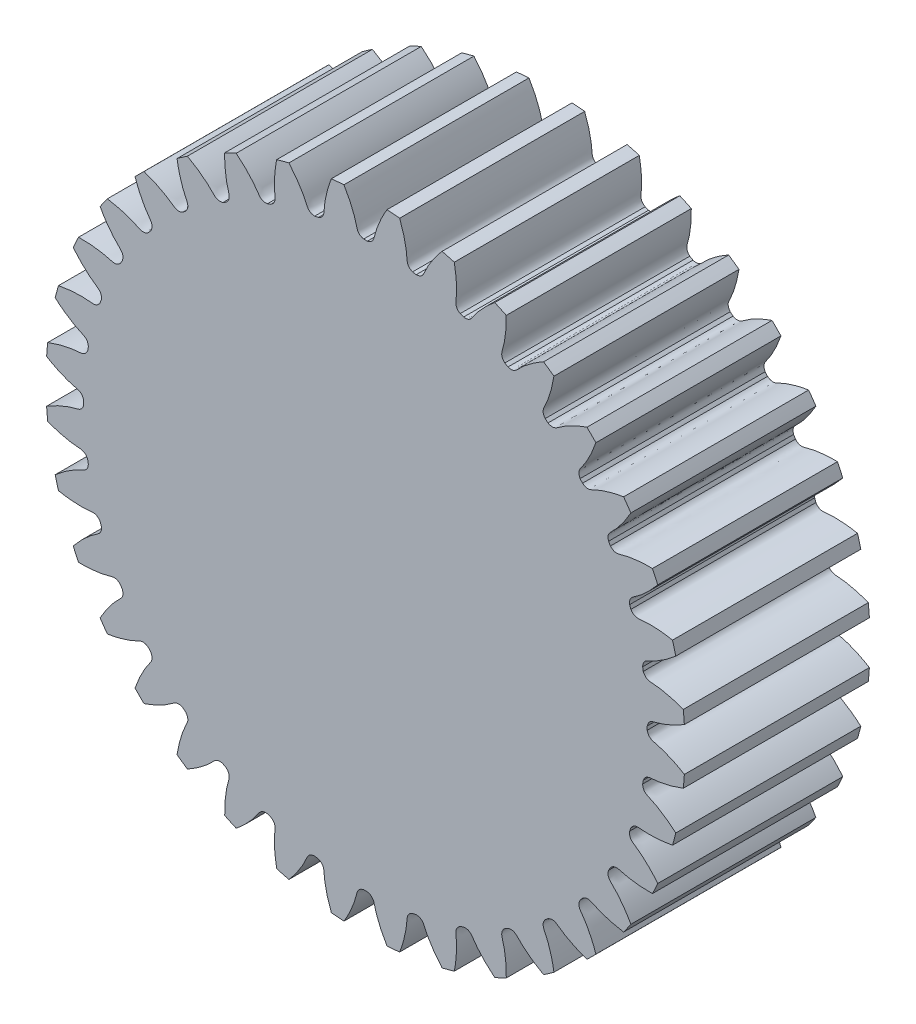
SolidWorks part; units mm, degrees
ref_plane "前视基准面" through (0, 0, 0) normal (0, 0, 1) x (1, 0, 0)
ref_plane "上视基准面" through (0, 0, 0) normal (0, 1, 0) x (1, 0, 0)
ref_plane "右视基准面" through (0, 0, 0) normal (1, 0, 0) x (0, 0, -1)
other "Configuration Table"
sketch "草图1" plane through (0, 0, 0) normal (0, 0, 1) x (1, 0, 0)
  circle A0 centre (0, 0) radius 9.5
extrude "凸台-拉伸1" add sketch "草图1" along normal blind 5.5
ref_axis "基准轴1" through (0, 0, 5.5) along (0, 0, -1)
sketch "草图2" plane through (0, 0, 0) normal (0, 0, 1) x (1, 0, 0)
  line L0 (0, 0) -> (0, 9.5) construction
  circle A0 centre (0, 0) radius 9.5 construction
  arc A1 (0.0549, 8.3748) -> (-0.0549, 8.3748) centre (0, 0) ccw
  arc A2 (1.757, 10.7884) -> (-1.757, 10.7884) centre (0, 0) ccw
  spline S0 degree 3 poles (0.0549, 8.3748) (0.235, 8.4152) (0.2505, 8.5493) (0.2882, 8.6914) (0.2997, 8.7319) (0.3131, 8.7753) (0.3284, 8.8217) (0.3457, 8.871) (0.3652, 8.9231) (0.3869, 8.9779) (0.4111, 9.0354) (0.4378, 9.0956) (0.4671, 9.1582) (0.4992, 9.2232) (0.5341, 9.2907) (0.5719, 9.3603) (0.6128, 9.4322) (0.6569, 9.5061) (0.7043, 9.582) (0.755, 9.6598) (0.8091, 9.7393) (0.8668, 9.8205) (0.9281, 9.9032) (0.9931, 9.9874) (1.0619, 10.0729) (1.1346, 10.1596) (1.2112, 10.2474) (1.2919, 10.3361) (1.3766, 10.4256) (1.4655, 10.5159) (1.5912, 10.6386) (1.6895, 10.7288) (1.757, 10.7884) knots 0 0 0 0 0.120371 0.133303 0.147364 0.162556 0.178878 0.19633 0.214913 0.234626 0.255469 0.277443 0.300547 0.324782 0.350146 0.376641 0.404267 0.433023 0.462909 0.493925 0.526072 0.559349 0.593757 0.629294 0.665963 0.703761 0.74269 0.782749 0.823939 0.866258 0.909709 1 1 1 1
  spline S1 degree 3 poles (-0.0549, 8.3748) (-0.235, 8.4152) (-0.2505, 8.5493) (-0.2882, 8.6914) (-0.2997, 8.7319) (-0.3131, 8.7753) (-0.3284, 8.8217) (-0.3457, 8.871) (-0.3652, 8.9231) (-0.3869, 8.9779) (-0.4111, 9.0354) (-0.4378, 9.0956) (-0.4671, 9.1582) (-0.4992, 9.2232) (-0.5341, 9.2907) (-0.5719, 9.3603) (-0.6128, 9.4322) (-0.6569, 9.5061) (-0.7043, 9.582) (-0.755, 9.6598) (-0.8091, 9.7393) (-0.8668, 9.8205) (-0.9281, 9.9032) (-0.9931, 9.9874) (-1.0619, 10.0729) (-1.1346, 10.1596) (-1.2112, 10.2474) (-1.2919, 10.3361) (-1.3766, 10.4256) (-1.4655, 10.5159) (-1.5912, 10.6386) (-1.6895, 10.7288) (-1.757, 10.7884) knots 0 0 0 0 0.120371 0.133303 0.147364 0.162556 0.178878 0.19633 0.214913 0.234626 0.255469 0.277443 0.300547 0.324782 0.350146 0.376641 0.404267 0.433023 0.462909 0.493925 0.526072 0.559349 0.593757 0.629294 0.665963 0.703761 0.74269 0.782749 0.823939 0.866258 0.909709 1 1 1 1
extrude "切除-拉伸1" cut sketch "草图2" along normal through all
pattern_circular "阵列(圆周)1" count 36 every 10 about axis through (0, 0, 5.5) along (0, 0, -1) of "切除-拉伸1"
sketch "草图3" plane through (0, 0, 0) normal (0, 0, 1) x (1, 0, 0)
  circle A0 centre (0, 0) radius 9 construction
  dimension "Dn" = 18
